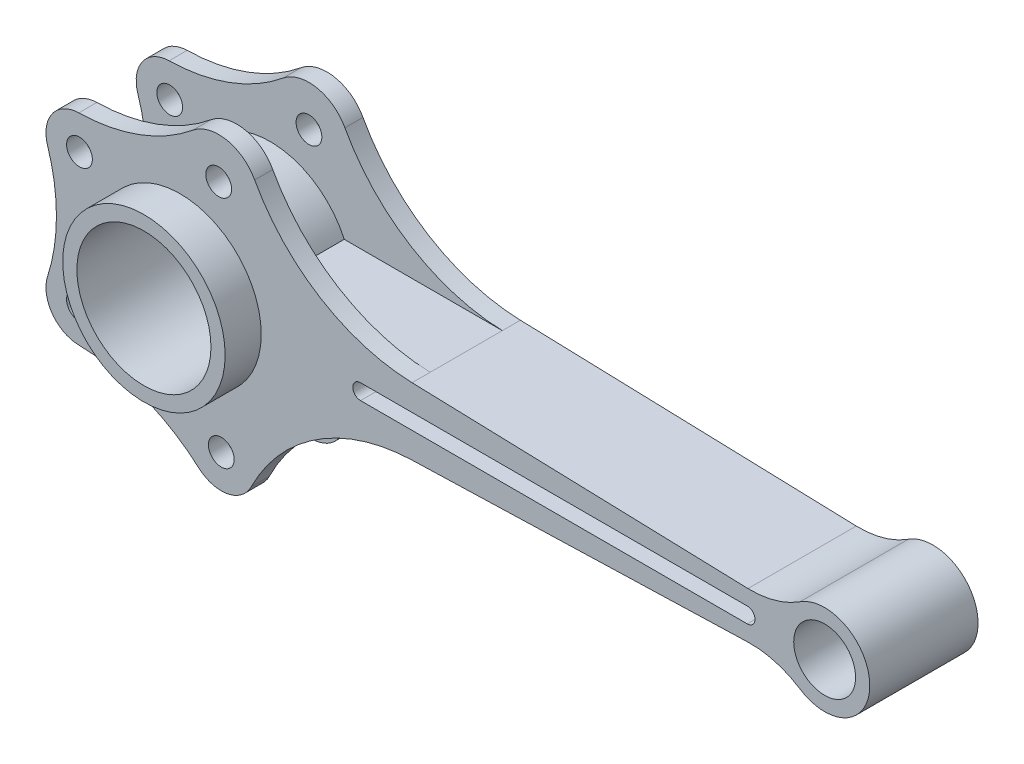
SolidWorks part; units mm, degrees
ref_plane "Front Plane" through (0, 0, 0) normal (0, 0, 1) x (1, 0, 0)
ref_plane "Top Plane" through (0, 0, 0) normal (0, 1, 0) x (1, 0, 0)
ref_plane "Right Plane" through (0, 0, 0) normal (1, 0, 0) x (0, 0, -1)
sketch "Sketch1" plane through (0, 0, 0) normal (0, 0, 1) x (1, 0, 0)
  line L0 (0, 0) -> (250, 0) construction
  line L1 (220.2604, 9) -> (90, 13)
  line L2 (220.2604, -9) -> (90, -13)
  line L3 (90, 13) -> (90, 0) construction
  line L4 (220, -3) -> (70, -3)
  line L5 (220, -3) -> (220, 3)
  line L6 (220, 3) -> (70, 3)
  line L7 (70, -3) -> (70, 3)
  line L8 (220, -3) -> (70, 3) construction
  line L9 (220, 3) -> (70, -3) construction
  line L10 (0, 0) -> (-147.7887, 0) construction
  line L11 (90, 13) -> (90, -13)
  line L12 (55, 0) -> (-55, 0) construction
  line L13 (90, 13) -> (28.6923, 13)
  line L14 (90, -13) -> (28.6923, -13)
  circle A0 centre (0, 0) radius 26
  circle A1 centre (0, 0) radius 31.5
  circle A2 centre (250, 0) radius 12
  arc A3 (240.4449, -14.6612) -> (240.4449, 14.6612) centre (250, 0) ccw
  arc A4 (70, 3) -> (70, -3) centre (70, 0) ccw
  arc A5 (220, 3) -> (220, -3) centre (220, 0) cw
  arc A6 (240.4449, -14.6612) -> (220.2604, -9) centre (221.3347, -43.9835) ccw
  arc A7 (220.2604, 9) -> (240.4449, 14.6612) centre (221.3347, 43.9835) ccw
  arc A8 (90, 13) -> (28.9504, 50.5825) centre (92.2099, 84.9661) cw
  arc A9 (28.9504, 50.5825) -> (4.9388, 55.2833) centre (15, 43) ccw
  arc A10 (4.9388, 55.2833) -> (-39.2577, 38.9974) centre (-40.6848, 110.9833) cw
  arc A11 (-39.2577, 38.9974) -> (-51.3769, 22.0235) centre (-39, 26) ccw
  arc A12 (-51.3769, 22.0235) -> (-51.3769, -22.0235) centre (-119.9259, 0) cw
  arc A13 (-51.3769, -22.0235) -> (-39.2012, -38.9984) centre (-39, -26) ccw
  arc A14 (-39.2012, -38.9984) -> (7.387, -57.0597) centre (-40.3157, -110.9898) cw
  arc A15 (7.387, -57.0597) -> (27.6556, -53.0796) centre (16, -47.3224) ccw
  arc A16 (27.6556, -53.0796) -> (90, -13) centre (92.2099, -84.9661) cw
  circle A17 centre (15, 43) radius 5
  circle A18 centre (-39, 26) radius 5
  circle A19 centre (-39, -26) radius 5
  circle A20 centre (16, -47.3224) radius 5
  point P9 (145, 0)
  point P21 (234.7339, -8.5556)
  point P24 (234.7339, 8.5556)
  point P43 (82.3885, 0)
  dimension "D1" = 52
  dimension "D2" = 63
  dimension "D3" = 24
  dimension "D4" = 35
  dimension "D5" = 6
  dimension "D7" = 150
  dimension "D8" = 30
  dimension "D9" = 13
  dimension "D10" = 130
  dimension "D11" = 35
  dimension "D12" = 18
  dimension "D13" = 72
  dimension "D17" = 72
  dimension "D18" = 13
  dimension "D19" = 72
  dimension "D20" = 13
  dimension "D21" = 13
  dimension "D24" = 72
  dimension "D25" = 72
  dimension "D27" = 10
  dimension "D28" = 10
  dimension "D29" = 10
  dimension "D30" = 10
  dimension "D6" = 250
  dimension "D14" = 15
  dimension "D15" = 39
  dimension "D16" = 26
  dimension "D22" = 16
  dimension "D23" = 39
  dimension "D26" = 17
extrude "Boss-Extrude1" add sketch "Sketch1" along normal mid plane 70 contours A1 A0 region at (29.9192, 6.4618, 0)
extrude "Boss-Extrude2" add sketch "Sketch1<9>" along normal mid plane 42 contours A7 L1 L11 L6 A5 L4 L2 A6 A3 A2 | A5 L5 | L7 L4 L5 L6 | L7 A4 | A16 L11 A4 A8 A1 region at (231.275, 8.5419, 0) region at (58.5233, 0, 0) region at (155, 0, 0) region at (221.2732, 0, 0) region at (68.7268, 0, 0)
sketch "Sketch1<9>" plane through (0, 0, 0) normal (0, 0, 1) x (1, 0, 0) same geometry as "Sketch1"
extrude "Boss-Extrude4" add sketch "Sketch1<13>" along normal up to surface (21 mm away) and the other way up to surface (21 mm away) contours L11 L6 L7 L4 region at (80, 0, 0) up to face at (80, 0, 21) other way up to face at (80, 0, -21)
sketch "Sketch1<13>" plane through (0, 0, 0) normal (0, 0, 1) x (1, 0, 0) same geometry as "Sketch1"
fillet "Fillet1" radius 72 2 edges at (28.6923, -13, 0) (28.6923, 13, 0)
extrude "Cut-Extrude1" cut sketch "Sketch1<10>" against normal through all from offset 2.5 contours L7 L4 L5 L6 | A5 L5 | L7 A4 | L5 L4 L7 L6 region at (155, 0, 0) region at (221.2732, 0, 0) region at (68.7268, 0, 0) offset against normal yes
sketch "Sketch1<10>" plane through (0, 0, 0) normal (0, 0, 1) x (1, 0, 0) same geometry as "Sketch1"
mirror "Mirror1" about plane through (0, 0, 0) normal (0, 0, 1) of "Cut-Extrude1"
extrude "Boss-Extrude3" add sketch "Sketch1<11>" along normal mid plane 42 contours A15 A16 L14 A1 L13 A8 A9 A10 A11 A12 A13 A14 A20 A19 A18 A17 region at (59.3462, 14.854, 0)
sketch "Sketch1<11>" plane through (0, 0, 0) normal (0, 0, 1) x (1, 0, 0) same geometry as "Sketch1"
extrude "Cut-Extrude2" cut sketch "Sketch1<12>" against normal mid plane 28 contours A15 A16 L14 A1 L13 A8 A9 A10 A11 A12 A13 A14 A20 A19 A18 A17 region at (59.3462, 14.854, 0)
sketch "Sketch1<12>" plane through (0, 0, 0) normal (0, 0, 1) x (1, 0, 0) same geometry as "Sketch1"
